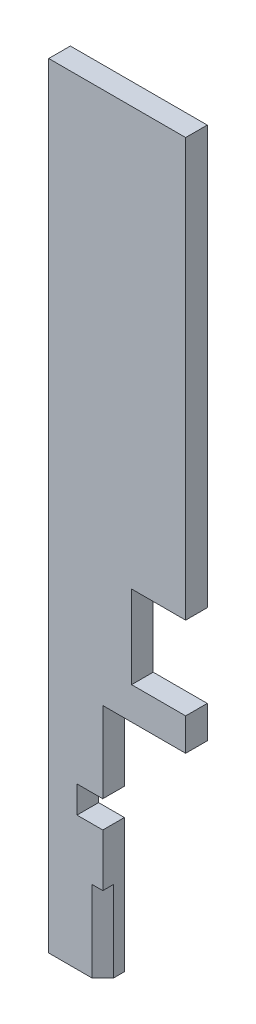
SolidWorks part; units mm, degrees
material "Plywood"
ref_plane "Plan de face" through (0, 0, 0) normal (0, 0, 1) x (1, 0, 0)
ref_plane "Plan de dessus" through (0, 0, 0) normal (0, 1, 0) x (1, 0, 0)
ref_plane "Plan de droite" through (0, 0, 0) normal (1, 0, 0) x (0, 0, -1)
sketch "Esquisse1" plane through (0, 0, 0) normal (0, 0, 1) x (1, 0, 0)
  line L0 (0, 0) -> (0, 215)
  line L1 (0, 215) -> (38, 215)
  line L2 (38, 215) -> (38, 0)
  line L3 (38, 0) -> (0, 0)
  dimension "D1" = 38
  dimension "D2" = 215
extrude "Boss.-Extru.1" add sketch "Esquisse1" along normal blind 6
sketch "Esquisse2" plane through (0, 0, 0) normal (0, 0, -1) x (-1, 0, 0)
  line L0 (-38, 0) -> (-38, 215) construction
  line L1 (-38, 76) -> (-23, 76)
  line L2 (-38, 76) -> (-38, 99)
  line L3 (-38, 99) -> (-23, 99)
  line L4 (-23, 76) -> (-23, 99)
  dimension "D1" = 15
extrude "Enlèv. mat.-Extru.1" cut sketch "Esquisse2" against normal through all
sketch "Esquisse3" plane through (0, 0, 6) normal (0, 0, 1) x (1, 0, 0)
  line L1 (38, 0) -> (18, 0)
  line L2 (38, 0) -> (38, 22.5)
  line L3 (38, 22.5) -> (18, 22.5)
  line L4 (18, 0) -> (18, 22.5)
  dimension "D1" = 20
  dimension "D2" = 22.5
extrude "Enlèv. mat.-Extru.2" cut sketch "Esquisse3" against normal blind 7.5
chamfer "Chanfrein1" distance 6 angle 45 1 edges at (18, 11.25, 6)
sketch "Esquisse4" plane through (0, 0, 0) normal (0, 0, -1) x (-1, 0, 0)
  line L0 (-38, 22.5) -> (-38, 76) construction
  line L1 (-38, 67) -> (-15, 67)
  line L2 (-38, 67) -> (-38, 0)
  line L3 (-38, 0) -> (-15, 0)
  line L4 (-15, 67) -> (-15, 0)
  line L5 (0, 0) -> (-18, 0) construction
  line L6 (0, 215) -> (0, 0) construction
  dimension "D1" = 15
  dimension "D2" = 67
extrude "Enlèv. mat.-Extru.3" cut sketch "Esquisse4" against normal through all
sketch "Esquisse5" plane through (0, 0, 0) normal (0, 0, -1) x (-1, 0, 0)
  line L0 (-15, 0) -> (-15, 67) construction
  line L1 (-15, 44.5754) -> (-7.8413, 44.5754)
  line L2 (-15, 44.5754) -> (-15, 37.0754)
  line L3 (-15, 37.0754) -> (-7.8413, 37.0754)
  line L4 (-7.8413, 44.5754) -> (-7.8413, 37.0754)
  line L5 (-30, 44.5754) -> (-38, 44.5754) construction
  line L6 (-30, 37.0754) -> (-38, 37.0754) construction
extrude "Enlèv. mat.-Extru.4" cut sketch "Esquisse5" against normal through all
sketch "Esquisse6" plane through (0, 0, 0) normal (0, -1, 0) x (-1, 0, 0)
  line L0 (0, -6) -> (-12, -6) construction
  line L1 (0, -6) -> (0, 0) construction
  circle A0 centre (-6, -3) radius 2.5
  dimension "D3" = 5
  dimension "D1" = 3
  dimension "D2" = 6
extrude "Enlèv. mat.-Extru.5" cut sketch "Esquisse6" against normal blind 10
